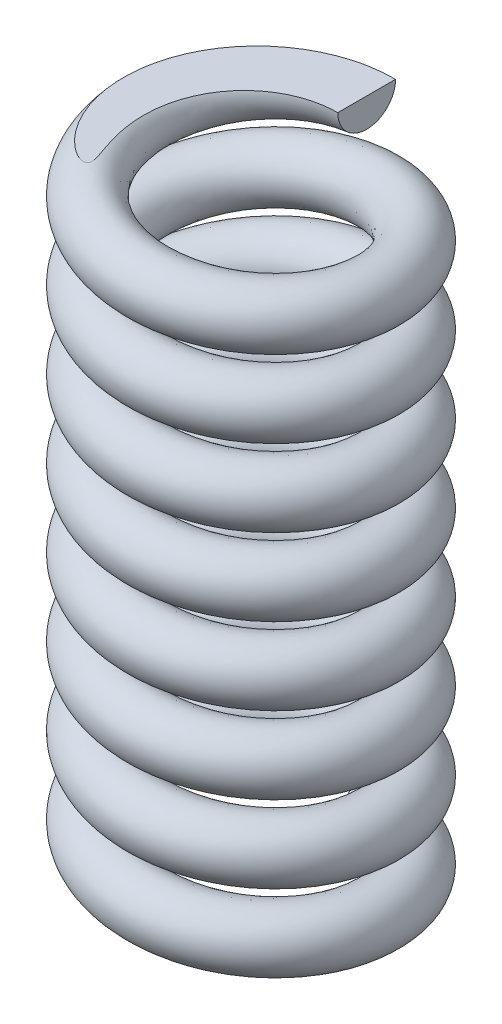
SolidWorks part; units mm, degrees
ref_plane "Front Plane" through (0, 0, 0) normal (0, 0, 1) x (1, 0, 0)
ref_plane "Top Plane" through (0, 0, 0) normal (0, 1, 0) x (1, 0, 0)
ref_plane "Right Plane" through (0, 0, 0) normal (1, 0, 0) x (0, 0, -1)
sketch "Sketch3" plane through (0, 0, 0) normal (0, 1, 0) x (1, 0, 0)
  circle A0 centre (0, 0) radius 60
  dimension "D1" = 120
curve "Helix/Spiral2" pitch 40 height 320 turns 8
sketch "Sketch4" plane through (0, 0, 0) normal (1, 0, 0) x (0, 0, -1)
  line L0 (60, 0) -> (0, 0) construction
  circle A0 centre (60, 0) radius 15
  spline S0 degree 3 poles (60, 0) (60, 0.3873) (59.3299, 1.1639) (56.3482, 2.3272) (51.489, 3.4909) (44.9145, 4.6545) (36.8435, 5.8182) (27.545, 6.9818) (17.3287, 8.1455) (6.5352, 9.3091) (-4.4761, 10.4727) (-15.3383, 11.6364) (-25.6894, 12.8) (-35.1846, 13.9636) (-43.5076, 15.1273) (-50.3811, 16.2909) (-55.576, 17.4545) (-58.9193, 18.6182) (-60.2996, 19.7818) (-59.6709, 20.9455) (-57.0541, 22.1091) (-52.5365, 23.2727) (-46.2685, 24.4364) (-38.459, 25.6) (-29.3682, 26.7636) (-19.2988, 27.9273) (-8.5866, 29.0909) (2.4118, 30.2545) (13.3298, 31.4182) (23.8037, 32.5818) (33.4845, 33.7455) (42.0497, 34.9091) (49.214, 36.0727) (54.7386, 37.2364) (58.4395, 38.4) (60.1934, 39.5636) (59.9417, 40.7273) (57.6931, 41.8909) (53.5222, 43.0545) (47.5682, 44.2182) (40.0294, 45.3818) (31.1569, 46.5455) (21.2463, 47.7091) (10.6279, 48.8727) (-0.3446, 50.0364) (-11.3057, 51.2) (-21.89, 52.3636) (-31.7451, 53.5273) (-40.5425, 54.6909) (-47.9891, 55.8545) (-53.8369, 57.0182) (-57.891, 58.1818) (-60.0164, 59.3455) (-60.1422, 60.5091) (-58.2643, 61.6727) (-54.4451, 62.8364) (-48.8121, 64) (-41.5527, 65.1636) (-32.909, 66.3273) (-23.1688, 67.4909) (-12.6567, 68.6545) (-1.7229, 69.8182) (9.2682, 70.9818) (19.9506, 72.1455) (29.9683, 73.3091) (38.9876, 74.4727) (46.7079, 75.6364) (52.872, 76.8) (57.2746, 77.9636) (59.769, 79.1273) (60.272, 80.2909) (58.767, 81.4545) (55.3041, 82.6182) (49.9986, 83.7818) (43.0273, 84.9455) (34.6224, 86.1091) (25.0641, 87.2727) (14.6707, 88.4364) (3.7885, 89.6) (-7.2199, 90.7636) (-17.9878, 91.9273) (-28.1564, 93.0909) (-37.3869, 94.2545) (-45.3717, 95.4182) (-51.845, 96.5818) (-56.5909, 97.7455) (-59.4514, 98.9091) (-60.3311, 100.0727) (-59.2008, 101.2364) (-56.0981, 102.4) (-51.1264, 103.5636) (-44.4513, 104.7273) (-36.2952, 105.8909) (-26.9299, 107.0545) (-16.6674, 108.2182) (-5.8496, 109.3818) (5.1632, 110.5455) (16.0039, 111.7091) (26.3114, 112.8727) (35.7423, 114.0364) (43.9823, 115.2) (50.7571, 116.3636) (55.8407, 117.5273) (59.0639, 118.6909) (60.3193, 119.8545) (59.565, 121.0182) (56.8262, 122.1818) (52.1941, 123.3455) (45.8231, 124.5091) (37.9254, 125.6727) (28.7641, 126.8364) (18.6445, 128) (7.9038, 129.1636) (-3.1003, 130.3273) (-14.0011, 131.4909) (-24.4355, 132.6545) (-34.0557, 133.8182) (-42.5413, 134.9818) (-49.6095, 136.1455) (-55.0249, 137.3091) (-58.6071, 138.4727) (-60.2366, 139.6364) (-59.8593, 140.8) (-57.4876, 141.9636) (-53.2006, 143.1273) (-47.1411, 144.2909) (-39.511, 145.4545) (-30.5646, 146.6182) (-20.5998, 147.7818) (-9.9487, 148.9455) (1.0338, 150.1091) (11.982, 151.2727) (22.5309, 152.4364) (32.3291, 153.6) (41.0503, 154.7636) (48.4037, 155.9273) (54.1446, 157.0909) (58.0814, 158.2545) (60.0832, 159.4182) (60.0832, 160.5818) (58.0814, 161.7455) (54.1446, 162.9091) (48.4037, 164.0727) (41.0503, 165.2364) (32.3291, 166.4) (22.5309, 167.5636) (11.982, 168.7273) (1.0338, 169.8909) (-9.9487, 171.0545) (-20.5998, 172.2182) (-30.5646, 173.3818) (-39.511, 174.5455) (-47.1411, 175.7091) (-53.2006, 176.8727) (-57.4876, 178.0364) (-59.8593, 179.2) (-60.2366, 180.3636) (-58.6071, 181.5273) (-55.0249, 182.6909) (-49.6095, 183.8545) (-42.5413, 185.0182) (-34.0557, 186.1818) (-24.4355, 187.3455) (-14.0011, 188.5091) (-3.1003, 189.6727) (7.9038, 190.8364) (18.6445, 192) (28.7641, 193.1636) (37.9254, 194.3273) (45.8231, 195.4909) (52.1941, 196.6545) (56.8262, 197.8182) (59.565, 198.9818) (60.3193, 200.1455) (59.0639, 201.3091) (55.8407, 202.4727) (50.7571, 203.6364) (43.9823, 204.8) (35.7423, 205.9636) (26.3114, 207.1273) (16.0039, 208.2909) (5.1632, 209.4545) (-5.8496, 210.6182) (-16.6674, 211.7818) (-26.9299, 212.9455) (-36.2952, 214.1091) (-44.4513, 215.2727) (-51.1264, 216.4364) (-56.0981, 217.6) (-59.2008, 218.7636) (-60.3311, 219.9273) (-59.4514, 221.0909) (-56.5909, 222.2545) (-51.845, 223.4182) (-45.3717, 224.5818) (-37.3869, 225.7455) (-28.1564, 226.9091) (-17.9878, 228.0727) (-7.2199, 229.2364) (3.7885, 230.4) (14.6707, 231.5636) (25.0641, 232.7273) (34.6224, 233.8909) (43.0273, 235.0545) (49.9986, 236.2182) (55.3041, 237.3818) (58.767, 238.5455) (60.272, 239.7091) (59.769, 240.8727) (57.2746, 242.0364) (52.872, 243.2) (46.7079, 244.3636) (38.9876, 245.5273) (29.9683, 246.6909) (19.9506, 247.8545) (9.2682, 249.0182) (-1.7229, 250.1818) (-12.6567, 251.3455) (-23.1688, 252.5091) (-32.909, 253.6727) (-41.5527, 254.8364) (-48.8121, 256) (-54.4451, 257.1636) (-58.2643, 258.3273) (-60.1422, 259.4909) (-60.0164, 260.6545) (-57.891, 261.8182) (-53.8369, 262.9818) (-47.9891, 264.1455) (-40.5425, 265.3091) (-31.7451, 266.4727) (-21.89, 267.6364) (-11.3057, 268.8) (-0.3446, 269.9636) (10.6279, 271.1273) (21.2463, 272.2909) (31.1569, 273.4545) (40.0294, 274.6182) (47.5682, 275.7818) (53.5222, 276.9455) (57.6931, 278.1091) (59.9417, 279.2727) (60.1934, 280.4364) (58.4395, 281.6) (54.7386, 282.7636) (49.214, 283.9273) (42.0497, 285.0909) (33.4845, 286.2545) (23.8037, 287.4182) (13.3298, 288.5818) (2.4118, 289.7455) (-8.5866, 290.9091) (-19.2988, 292.0727) (-29.3682, 293.2364) (-38.459, 294.4) (-46.2685, 295.5636) (-52.5365, 296.7273) (-57.0541, 297.8909) (-59.6709, 299.0545) (-60.2996, 300.2182) (-58.9193, 301.3818) (-55.576, 302.5455) (-50.3811, 303.7091) (-43.5076, 304.8727) (-35.1846, 306.0364) (-25.6894, 307.2) (-15.3383, 308.3636) (-4.4761, 309.5273) (6.5352, 310.6909) (17.3287, 311.8545) (27.545, 313.0182) (36.8435, 314.1818) (44.9145, 315.3455) (51.489, 316.5091) (56.3482, 317.6728) (59.3299, 318.8361) (60, 319.6127) (60, 320) knots 0 0 0 0 0.003636 0.007273 0.010909 0.014545 0.018182 0.021818 0.025455 0.029091 0.032727 0.036364 0.04 0.043636 0.047273 0.050909 0.054545 0.058182 0.061818 0.065455 0.069091 0.072727 0.076364 0.08 0.083636 0.087273 0.090909 0.094545 0.098182 0.101818 0.105455 0.109091 0.112727 0.116364 0.12 0.123636 0.127273 0.130909 0.134545 0.138182 0.141818 0.145455 0.149091 0.152727 0.156364 0.16 0.163636 0.167273 0.170909 0.174545 0.178182 0.181818 0.185455 0.189091 0.192727 0.196364 0.2 0.203636 0.207273 0.210909 0.214545 0.218182 0.221818 0.225455 0.229091 0.232727 0.236364 0.24 0.243636 0.247273 0.250909 0.254545 0.258182 0.261818 0.265455 0.269091 0.272727 0.276364 0.28 0.283636 0.287273 0.290909 0.294545 0.298182 0.301818 0.305455 0.309091 0.312727 0.316364 0.32 0.323636 0.327273 0.330909 0.334545 0.338182 0.341818 0.345455 0.349091 0.352727 0.356364 0.36 0.363636 0.367273 0.370909 0.374545 0.378182 0.381818 0.385455 0.389091 0.392727 0.396364 0.4 0.403636 0.407273 0.410909 0.414545 0.418182 0.421818 0.425455 0.429091 0.432727 0.436364 0.44 0.443636 0.447273 0.450909 0.454545 0.458182 0.461818 0.465455 0.469091 0.472727 0.476364 0.48 0.483636 0.487273 0.490909 0.494545 0.498182 0.501818 0.505455 0.509091 0.512727 0.516364 0.52 0.523636 0.527273 0.530909 0.534545 0.538182 0.541818 0.545455 0.549091 0.552727 0.556364 0.56 0.563636 0.567273 0.570909 0.574545 0.578182 0.581818 0.585455 0.589091 0.592727 0.596364 0.6 0.603636 0.607273 0.610909 0.614545 0.618182 0.621818 0.625455 0.629091 0.632727 0.636364 0.64 0.643636 0.647273 0.650909 0.654545 0.658182 0.661818 0.665455 0.669091 0.672727 0.676364 0.68 0.683636 0.687273 0.690909 0.694545 0.698182 0.701818 0.705455 0.709091 0.712727 0.716364 0.72 0.723636 0.727273 0.730909 0.734545 0.738182 0.741818 0.745455 0.749091 0.752727 0.756364 0.76 0.763636 0.767273 0.770909 0.774545 0.778182 0.781818 0.785455 0.789091 0.792727 0.796364 0.8 0.803636 0.807273 0.810909 0.814545 0.818182 0.821818 0.825455 0.829091 0.832727 0.836364 0.84 0.843636 0.847273 0.850909 0.854545 0.858182 0.861818 0.865455 0.869091 0.872727 0.876364 0.88 0.883636 0.887273 0.890909 0.894545 0.898182 0.901818 0.905455 0.909091 0.912727 0.916364 0.92 0.923636 0.927273 0.930909 0.934545 0.938182 0.941818 0.945455 0.949091 0.952727 0.956364 0.96 0.963636 0.967273 0.970909 0.974545 0.978182 0.981818 0.985455 0.989091 0.992727 0.996364 1 1 1 1 construction
  dimension "D1" = 30
sweep "Sweep1" add profiles "Sketch4" path "Helix/Spiral2"
sketch "Sketch5" plane through (0, 0, 0) normal (1, 0, 0) x (0, 0, -1)
  line L1 (75, 0) -> (-75, 0)
  line L2 (75, 0) -> (75, -40)
  line L3 (75, -40) -> (-75, -40)
  line L4 (-75, 0) -> (-75, -40)
  line L5 (75, 320) -> (-75, 320)
  line L6 (75, 320) -> (75, 358.0715)
  line L7 (75, 358.0715) -> (-75, 358.0715)
  line L8 (-75, 320) -> (-75, 358.0715)
  circle A0 centre (60, 0) radius 15 construction
  circle A1 centre (60, 320) radius 15 construction
  dimension "D1" = 150
  dimension "D2" = 40
  dimension "D3" = 38.0715
  dimension "D4" = 150
  dimension "D5" = 320
extrude "Cut-Extrude1" cut sketch "Sketch5" against normal mid plane 170
